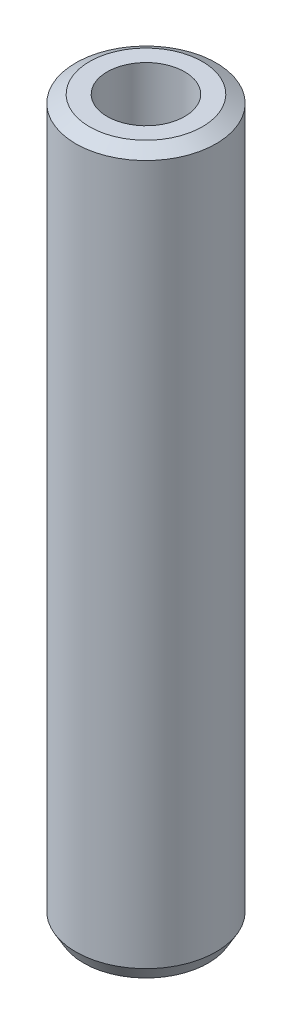
SolidWorks part; units mm, degrees
ref_plane "Front Plane" through (0, 0, 0) normal (0, 0, 1) x (1, 0, 0)
ref_plane "Top Plane" through (0, 0, 0) normal (0, 1, 0) x (1, 0, 0)
ref_plane "Right Plane" through (0, 0, 0) normal (1, 0, 0) x (0, 0, -1)
sketch "Sketch1" plane through (0, 0, 0) normal (0, 1, 0) x (1, 0, 0)
  circle A0 centre (0, 0) radius 7.5
  dimension "SHAFT_OD" = 15
extrude "Boss-Extrude1" add sketch "Sketch1" along normal blind 77.1191
sketch "Sketch2" plane through (0, 0, 0) normal (0, 1, 0) x (1, 0, 0)
  circle A0 centre (0, 0) radius 4.1426
  dimension "BORE_D" = 8.2852
extrude "Cut-Extrude1" cut sketch "Sketch2" along normal through all
chamfer "Chamfer1" distance 0.8447 angle 60 2 edges at (0, 77.1191, 7.5) (0, 0, 7.5) first distance on face at (0, 77.1191, 7.5) first distance on face at (0, 0, 4.1426)
